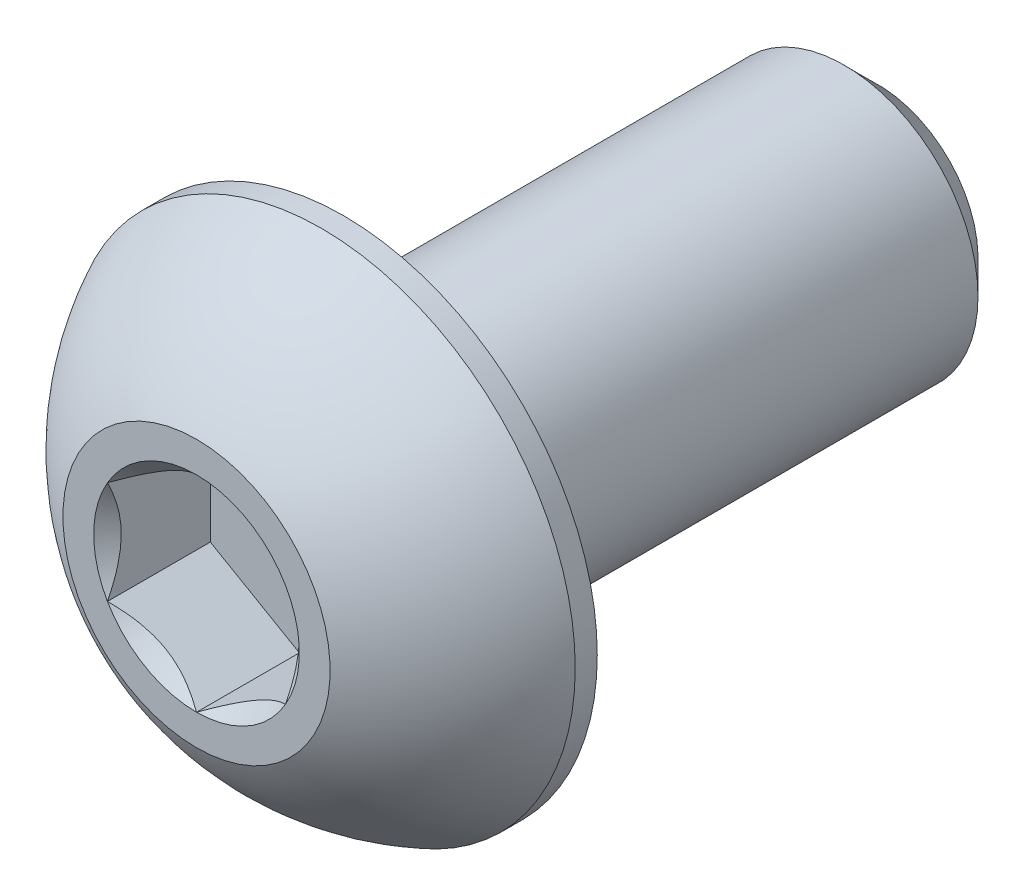
SolidWorks part; units mm, degrees
ref_plane "Front" through (0, 0, 0) normal (0, 0, 1) x (1, 0, 0)
ref_plane "Top" through (0, 0, 0) normal (0, 1, 0) x (1, 0, 0)
ref_plane "Right" through (0, 0, 0) normal (1, 0, 0) x (0, 0, -1)
sketch "Sketch1" plane through (0, 0, 0) normal (1, 0, 0) x (0, 0, -1)
  line L2 (1.65, 1.5) -> (7.65, 1.5)
  line L3 (7.65, 1.5) -> (7.65, 0)
  line L4 (7.65, 0) -> (1.65, 0)
  line L6 (1.4025, 2.85) -> (1.65, 2.85) construction
  line L7 (7.65, 1.5) -> (7.65, -1.5) construction
  line L8 (0, 0) -> (1.65, 0) construction
  line L9 (1.65, 2.85) -> (1.65, -2.85) construction
  line L11 (1.65, 1.5) -> (1.65, 0)
  line L13 (0, 1) -> (0, -1) construction
  line L14 (0, 1) -> (0, 1.5) construction
  arc A3 (0, 1.5) -> (1.4025, 2.85) centre (2.7948, 0) cw construction
  dimension "D1" = 0.2475
revolve "Revolve1" add sketch "Sketch1" angle 360 mid plane about L4
sketch "Sketch3" plane through (0, 0, -7.65) normal (0, 0, -1) x (-1, 0, 0)
  circle A0 centre (0, 0) radius 1.5
curve "Helix/Spiral1" pitch 0.5 height 6.5 turns 13
sketch "Sketch2" plane through (0, 0, 0) normal (1, 0, 0) x (0, 0, -1)
  line L0 (7.65, 1.5) -> (8.0875, 1.5)
  line L1 (8.0875, 1.5) -> (7.9, 1.1752)
  line L2 (7.9, 1.1752) -> (7.8375, 1.1752)
  line L3 (7.8375, 1.1752) -> (7.65, 1.5)
  line L4 (7.7438, 1.3376) -> (7.9938, 1.3376) construction
  dimension "D1" = 60
  dimension "D2" = 0.0625
  dimension "D3" = 0.25
chamfer "Chamfer1" distance 0.375 angle 45 1 edges at (0, 1.5, -7.65)
sweep "Cut-Sweep1" [suppressed] cut profiles "Sketch2" path "Helix/Spiral1"
sketch "Sketch7" plane through (0, 0, 0) normal (1, 0, 0) x (0, 0, -1)
  line L6 (1.4025, 2.85) -> (1.65, 2.85) construction
  line L8 (0, 0) -> (1.65, 0) construction
  line L11 (1.65, 2.85) -> (1.65, -2.85) construction
  line L12 (1.4025, 2.85) -> (1.65, 2.85)
  line L13 (0, 0) -> (1.65, 0)
  line L14 (0, 1) -> (0, -1) construction
  line L15 (1.65, 2.85) -> (1.65, 0)
  line L16 (0, 1.5) -> (0, 0)
  arc A2 (1.4025, 2.85) -> (0, 1.5) centre (2.7948, 0) ccw construction
  arc A3 (1.4025, 2.85) -> (0, 1.5) centre (2.7948, 0) ccw
revolve "Revolve2" add sketch "Sketch7" angle 360 mid plane about L13
sketch "Sketch5" plane through (0, 0, 0) normal (0, 0, 1) x (1, 0, 0)
  line L1 (1, -0.5774) -> (1, 0.5774)
  line L2 (1, 0.5774) -> (0, 1.1547)
  line L3 (0, 1.1547) -> (-1, 0.5774)
  line L4 (-1, 0.5774) -> (-1, -0.5774)
  line L5 (-1, -0.5774) -> (0, -1.1547)
  line L6 (0, -1.1547) -> (1, -0.5774)
  circle A0 centre (0, 0) radius 1 construction
extrude "Cut-Extrude2" cut sketch "Sketch5" against normal blind 1.155
sketch "Sketch6" plane through (0, 0, 0) normal (0, 0, 1) x (1, 0, 0)
  circle A0 centre (0, 0) radius 1.1547
extrude "Cut-Extrude3" cut sketch "Sketch6" against normal blind 1.155 draft 45
sketch "Sketch9" [suppressed] plane through (0, 0, -4.2164) normal (0, 0, 1) x (1, 0, 0)
  circle A2 centre (0, 0) radius 3.9687
extrude "Boss-Extrude2" [suppressed] add sketch "Sketch9" against normal offset from surface (9.525 mm away) 28.575 up to face at (0, 1.125, -7.65)
sketch "Sketch10" [suppressed] plane through (0, 0, 0) normal (1, 0, 0) x (0, 0, -1)
  line L0 (7.65, 1.5) -> (7.65, -1.5) construction
  point P0 (6.9, -1.5)
  dimension "D1" = 0.75
equation "\"D3@Helix/Spiral1\" = \"Lg@Sketch1\" + \"D4@Helix/Spiral1\""
equation "\"D2@Sketch2\" = \"D4@Helix/Spiral1\" * .125"
equation "\"D3@Sketch2\" = \"D4@Helix/Spiral1\" * .5"
equation "\"D1@Chamfer1\" = \"D4@Helix/Spiral1\" * .75"
equation "\"D1@Cut-Extrude2\" = \"Head Ht@Sketch1\" * .7"
equation "\"D1@Sketch1\" = \"Head Ht@Sketch1\" * .15"
equation "\"D1@Sketch10\" = \"D4@Helix/Spiral1\" * 1.5"
equation "\"D1@Cut-Extrude3\" = \"D1@Cut-Extrude2\""
